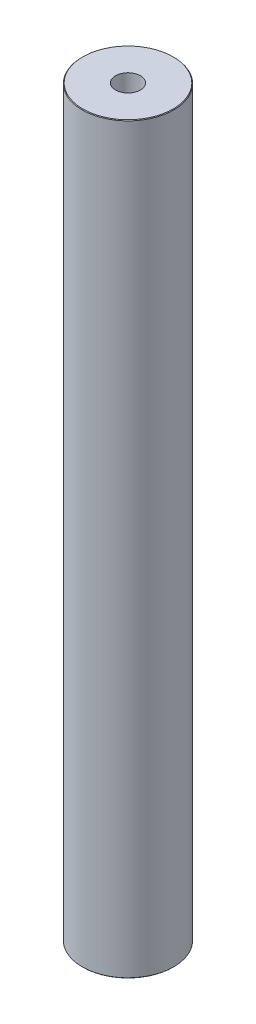
SolidWorks part; units mm, degrees
ref_plane "Front Plane" through (0, 0, 0) normal (0, 0, 1) x (1, 0, 0)
ref_plane "Top Plane" through (0, 0, 0) normal (0, 1, 0) x (1, 0, 0)
ref_plane "Right Plane" through (0, 0, 0) normal (1, 0, 0) x (0, 0, -1)
sketch "Sketch1" plane through (0, 0, 0) normal (0, 1, 0) x (1, 0, 0)
  circle A0 centre (0, 0) radius 20
  dimension "SHAFT_OD" = 40
extrude "Boss-Extrude1" add sketch "Sketch1" along normal blind 324.9267
sketch "Sketch2" plane through (0, 0, 0) normal (0, 1, 0) x (1, 0, 0)
  circle A0 centre (0, 0) radius 5.4382
  dimension "BORE_D" = 10.8763
extrude "Cut-Extrude1" cut sketch "Sketch2" along normal through all
chamfer "Chamfer1" distance 0.2562 angle 45 2 edges at (0, 324.9267, 20) (0, 0, 20)
